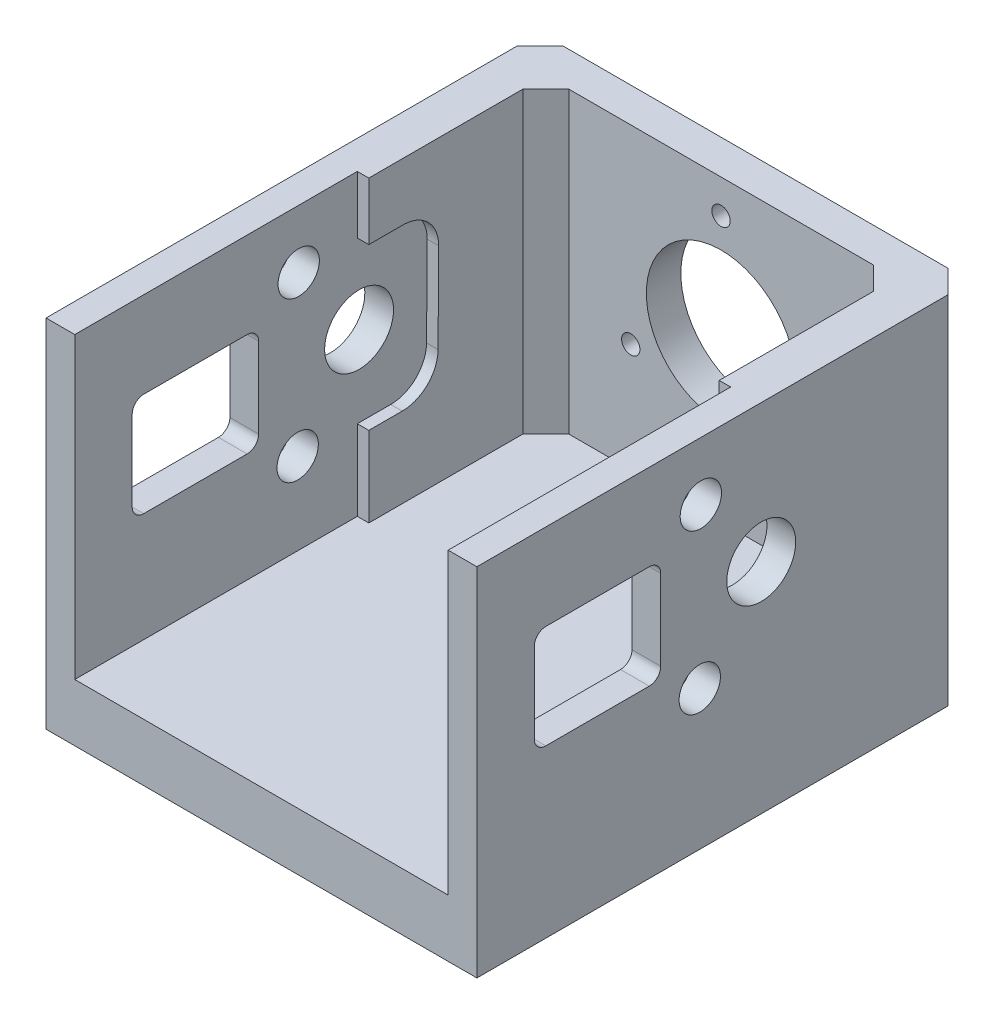
SolidWorks part; units mm, degrees
ref_plane "Front Plane" through (0, 0, 0) normal (0, 0, 1) x (1, 0, 0)
ref_plane "Top Plane" through (0, 0, 0) normal (0, 1, 0) x (1, 0, 0)
ref_plane "Right Plane" through (0, 0, 0) normal (1, 0, 0) x (0, 0, -1)
sketch "Sketch1" plane through (0, 0, 0) normal (0, 0, 1) x (1, 0, 0)
  line L0 (18.75, 0) -> (-18.75, 0) construction
  line L2 (-18.75, 12) -> (18.75, 12)
  line L3 (-18.75, 12) -> (-18.75, -12)
  line L4 (-18.75, -12) -> (18.75, -12)
  line L5 (18.75, 12) -> (18.75, -12)
  circle A0 centre (0, 0) radius 12 construction
  circle A1 centre (0, 0) radius 9.075 construction
  circle A2 centre (0, 9.075) radius 0.8
  circle A3 centre (7.8592, -4.5375) radius 0.8
  circle A4 centre (-7.8592, -4.5375) radius 0.8
  circle A5 centre (0, 0) radius 6.5
  point P12 (0, 0)
  point P15 (0, 0)
  point P19 (0, 0)
  point P20 (0, 0)
  dimension "D1" = 24
  dimension "D2" = 18.15
  dimension "D3" = 1.6
  dimension "D5" = 13
  dimension "D6" = 18.75
  dimension "D4" = 3
extrude "Boss-Extrude1" add sketch "Sketch1" against normal blind 3
sketch "Sketch2" plane through (0, 12, 0) normal (0, 1, 0) x (1, 0, 0)
  line L1 (-18.75, 0) -> (-16.25, 0)
  line L2 (-18.75, 0) -> (-18.75, -40)
  line L3 (-18.75, -40) -> (-16.25, -40)
  line L4 (-16.25, 0) -> (-16.25, -40)
  line L5 (18.75, 0) -> (16.25, 0)
  line L6 (18.75, 0) -> (18.75, -40)
  line L7 (18.75, -40) -> (16.25, -40)
  line L8 (16.25, 0) -> (16.25, -40)
  dimension "D1" = 2.5
  dimension "D2" = 40
extrude "Boss-Extrude2" add sketch "Sketch2" against normal up to surface (24 mm away) up to face at (0, -12, -1.5)
sketch "Sketch4" plane through (-16.25, 0, 0) normal (1, 0, 0) x (0, 0, -1)
  line L0 (-9.4284, 3.8618) -> (-9.4797, -3.9381) construction
  line L1 (-9.4284, 3.8618) -> (-9.4797, -3.9381) construction
  line L2 (-9.3284, 3.8611) -> (-9.3797, -3.9387)
  line L3 (-12.408, 6.9814) -> (-15.408, 6.9814)
  line L4 (-15.408, 6.9814) -> (-15.408, 12)
  line L5 (-40, 12) -> (0, 12) construction
  line L6 (-15.408, 12) -> (0, 12)
  line L7 (0, 12) -> (0, -12)
  line L8 (0, -12) -> (-15.408, -12)
  line L9 (-40, -12) -> (0, -12) construction
  line L10 (-15.408, -12) -> (-15.408, -7.0183)
  line L11 (-12.5, -7.0183) -> (-15.408, -7.0183)
  arc A0 (-9.4284, 3.8618) -> (-12.4086, 6.8814) centre (-12.4295, 3.8804) ccw construction
  arc A1 (-12.4994, -6.9183) -> (-9.4797, -3.9381) centre (-12.4808, -3.9172) ccw construction
  arc A2 (-12.4994, -6.9183) -> (-9.4797, -3.9381) centre (-12.4808, -3.9172) ccw construction
  arc A3 (-9.4284, 3.8618) -> (-12.4086, 6.8814) centre (-12.4295, 3.8804) ccw construction
  arc A4 (-9.3284, 3.8611) -> (-12.408, 6.9814) centre (-12.4295, 3.8804) ccw
  arc A5 (-12.5, -7.0183) -> (-9.3797, -3.9387) centre (-12.4808, -3.9172) ccw
  dimension "D2" = 3
  dimension "D1" = 0.1
extrude "Boss-Extrude3" add sketch "Sketch4" along normal blind 1
extrude "Boss-Extrude4" add sketch "Sketch4<2>" against normal blind 1 from surface starting at face at (16.25, 0, 20)
sketch "Sketch4<2>" plane through (-16.25, 0, 0) normal (1, 0, 0) x (0, 0, -1) same geometry as "Sketch4"
hole_wizard "M3 Clearance Hole1" positions "Sketch5" profile "Sketch6" hole size "M3" standard "DIN" end condition through all
sketch "Sketch5" plane through (-18.75, 0, 0) normal (1, 0, 0) x (0, 0, -1)
  arc A0 (-18.9993, -6.8755) -> (-22.1992, -6.8545) centre (-20.5992, -6.865) ccw construction
  arc A1 (-22.1084, 6.9452) -> (-18.9085, 6.9242) centre (-20.5085, 6.9347) ccw construction
  arc A2 (-18.9993, -6.8755) -> (-22.1992, -6.8545) centre (-20.5992, -6.865) ccw
  arc A3 (-22.1084, 6.9452) -> (-18.9085, 6.9242) centre (-20.5085, 6.9347) ccw
  point P7 (-20.5085, 6.9347)
  point P9 (-20.5992, -6.865)
sketch "Sketch6" plane through (-18.75, -6.865, 20.5992) normal (0, 1, 0) x (0, 0, 1)
  line L0 (0, 0) -> (0, 37.5)
  line L1 (0, 37.5) -> (1.8, 37.5)
  line L2 (1.8, 37.5) -> (1.8, 0)
  line L5 (1.8, 0) -> (0, 0)
  line L11 (0, -6.35) -> (0, 107.95) construction
  dimension "Thru Hole Dia." = 3.6
  dimension "Thru Hole Depth" = 37.5
chamfer "Chamfer1" distance 2 angle 45 4 edges at (18.75, 0, -3) (-18.75, 0, -3) (15.25, 0, 0) (-15.25, 0, 0)
sketch "Sketch7" plane through (-18.75, 0, 0) normal (-1, 0, 0) x (0, 0, 1)
  line L0 (40, 0) -> (35, 0) construction
  line L1 (24, 4.5) -> (35, 4.5)
  line L2 (24, 4.5) -> (24, -4.5)
  line L3 (24, -4.5) -> (35, -4.5)
  line L4 (35, 4.5) -> (35, -4.5)
  line L5 (40, -12) -> (40, 12) construction
  circle A0 centre (15.254, 0) radius 3
  point P8 (15.254, 0)
  dimension "D4" = 6
  dimension "D1" = 11
  dimension "D2" = 5
  dimension "D3" = 9
extrude "Cut-Extrude1" cut sketch "Sketch7" against normal through all
fillet "Fillet1" radius 1 8 edges at (17.5, -4.5, 24) (17.5, 4.5, 24) (17.5, 4.5, 35) (17.5, -4.5, 35) (-17.5, -4.5, 35) (-17.5, 4.5, 35) (-17.5, 4.5, 24) (-17.5, -4.5, 24)
sketch "Sketch8" plane through (0, -12, 0) normal (0, -1, 0) x (1, 0, 0)
  line L16 (-16.75, -3) -> (16.75, -3)
  line L17 (16.75, -3) -> (18.75, -1)
  line L18 (18.75, -1) -> (18.75, 40)
  line L19 (18.75, 40) -> (16.25, 40)
  line L20 (16.25, 40) -> (16.25, 15.408)
  line L21 (16.25, 15.408) -> (15.25, 15.408)
  line L22 (15.25, 15.408) -> (15.25, 2)
  line L23 (15.25, 2) -> (13.25, 0)
  line L24 (13.25, 0) -> (-13.25, 0)
  line L25 (-13.25, 0) -> (-15.25, 2)
  line L26 (-15.25, 2) -> (-15.25, 15.408)
  line L27 (-15.25, 15.408) -> (-16.25, 15.408)
  line L28 (-16.25, 15.408) -> (-16.25, 40)
  line L29 (-16.25, 40) -> (-18.75, 40)
  line L30 (-18.75, 40) -> (-18.75, -1)
  line L31 (-18.75, -1) -> (-16.75, -3)
  line L32 (-16.75, -3) -> (16.75, -3)
  line L33 (16.75, -3) -> (18.75, -1)
  line L34 (18.75, -1) -> (18.75, 40)
  line L35 (18.75, 40) -> (16.25, 40)
  line L36 (16.25, 40) -> (16.25, 15.408)
  line L37 (16.25, 15.408) -> (15.25, 15.408)
  line L38 (15.25, 15.408) -> (15.25, 2)
  line L39 (15.25, 2) -> (13.25, 0)
  line L40 (13.25, 0) -> (-13.25, 0)
  line L41 (-13.25, 0) -> (-15.25, 2)
  line L42 (-15.25, 2) -> (-15.25, 15.408)
  line L43 (-15.25, 15.408) -> (-16.25, 15.408)
  line L44 (-16.25, 15.408) -> (-16.25, 40)
  line L45 (-16.25, 40) -> (-18.75, 40)
  line L46 (-18.75, 40) -> (-18.75, -1)
  line L47 (-18.75, -1) -> (-16.75, -3)
  dimension "D1" = 0
extrude "Boss-Extrude5" add sketch "Sketch8" along normal blind 2
sketch "Sketch9" plane through (0, -14, 0) normal (0, -1, 0) x (1, 0, 0)
  line L0 (-18.75, 40) -> (18.75, 40)
  line L16 (-18.75, -1) -> (-16.75, -3)
  line L17 (-16.75, -3) -> (16.75, -3)
  line L18 (16.75, -3) -> (18.75, -1)
  line L19 (18.75, -1) -> (18.75, 40)
  line L20 (18.75, 40) -> (16.25, 40)
  line L21 (16.25, 40) -> (16.25, 15.408)
  line L22 (16.25, 15.408) -> (15.25, 15.408)
  line L23 (15.25, 15.408) -> (15.25, 2)
  line L24 (15.25, 2) -> (13.25, 0)
  line L25 (13.25, 0) -> (-13.25, 0)
  line L26 (-13.25, 0) -> (-15.25, 2)
  line L27 (-15.25, 2) -> (-15.25, 15.408)
  line L28 (-15.25, 15.408) -> (-16.25, 15.408)
  line L29 (-16.25, 15.408) -> (-16.25, 40)
  line L30 (-16.25, 40) -> (-18.75, 40)
  line L31 (-18.75, 40) -> (-18.75, -1)
  line L32 (-18.75, -1) -> (-16.75, -3)
  line L33 (-16.75, -3) -> (16.75, -3)
  line L34 (16.75, -3) -> (18.75, -1)
  line L35 (18.75, -1) -> (18.75, 40)
  line L47 (-18.75, 40) -> (-18.75, -1)
  dimension "D1" = 0
extrude "Boss-Extrude6" add sketch "Sketch9" along normal blind 5
